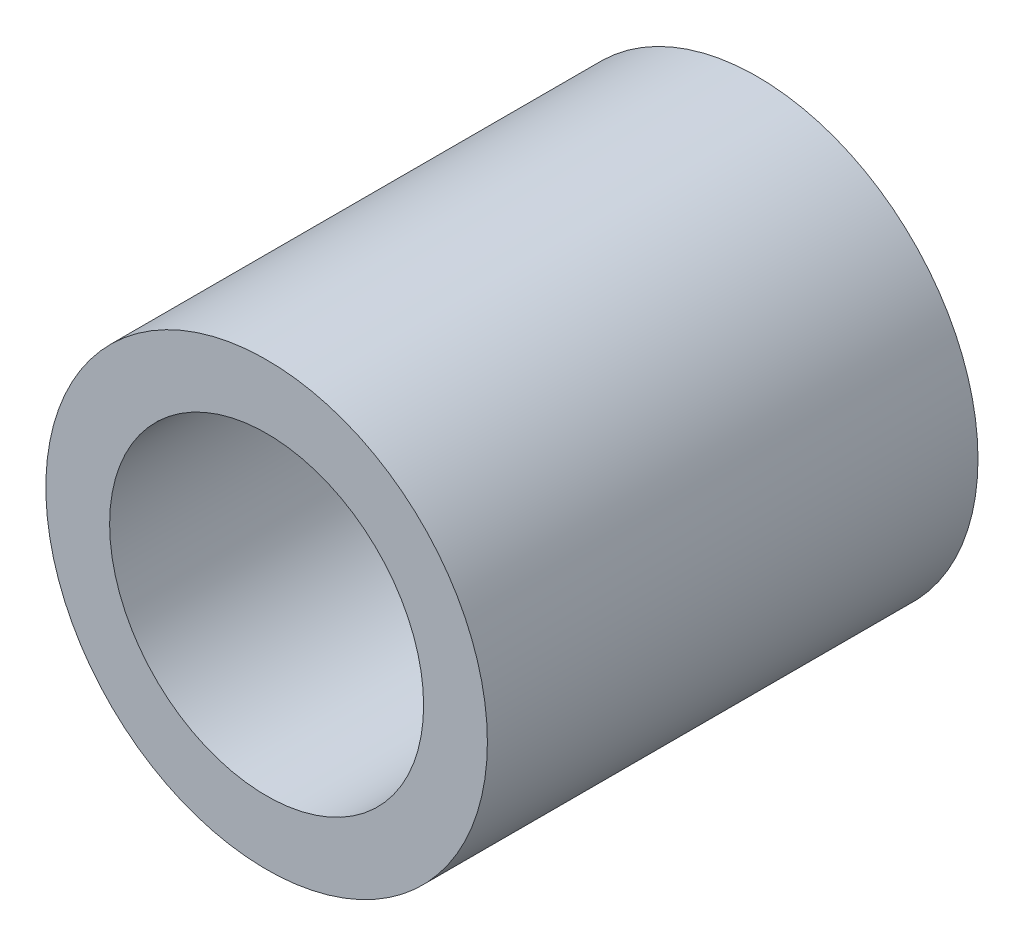
SolidWorks part; units mm, degrees
ref_plane "Front Plane" through (0, 0, 0) normal (0, 0, 1) x (1, 0, 0)
ref_plane "Top Plane" through (0, 0, 0) normal (0, 1, 0) x (1, 0, 0)
ref_plane "Right Plane" through (0, 0, 0) normal (1, 0, 0) x (0, 0, -1)
sketch "Sketch3" plane through (0, 0, 0) normal (0, 0, 1) x (1, 0, 0)
  circle A0 centre (0, 0) radius 1.6 construction
  circle A1 centre (0, 0) radius 2.25 construction
  point P6 (0, -1.6)
  dimension "OD" = 4.5
  dimension "ID" = 3.2
sketch "Sketch1" plane through (0, 0, 0) normal (1, 0, 0) x (0, 0, -1)
  line L0 (-2.5, -1.6) -> (-2.5, 1.6) construction
  line L1 (2.5, -2.25) -> (-2.5, -2.25) construction
  line L2 (2.5, -2.25) -> (2.5, 2.25) construction
  line L3 (2.5, 2.25) -> (-2.5, 2.25) construction
  line L4 (-2.5, -2.25) -> (-2.5, 2.25) construction
  line L5 (0, 2.25) -> (0, -2.25) construction
  line L6 (2.5, 0) -> (-2.5, 0) construction
  point P0 (0, 0)
  point P7 (-2.5, 0)
  dimension "OD" = 4.5
  dimension "ID" = 3.2
sketch "Sketch2" plane through (0, 0, 0) normal (0, 0, 1) x (1, 0, 0)
  circle A0 centre (0, 0) radius 2.25
  circle A1 centre (0, 0) radius 1.6
extrude "Extrude1" add sketch "Sketch2" along normal up to vertex and the other way up to vertex up to point (0, -2.25, 2.5) other way up to point (0, 2.25, -2.5)
equation "\"ID@Sketch1\" = \"ID@Sketch3\""
equation "\"OD@Sketch1\" = \"OD@Sketch3\""
